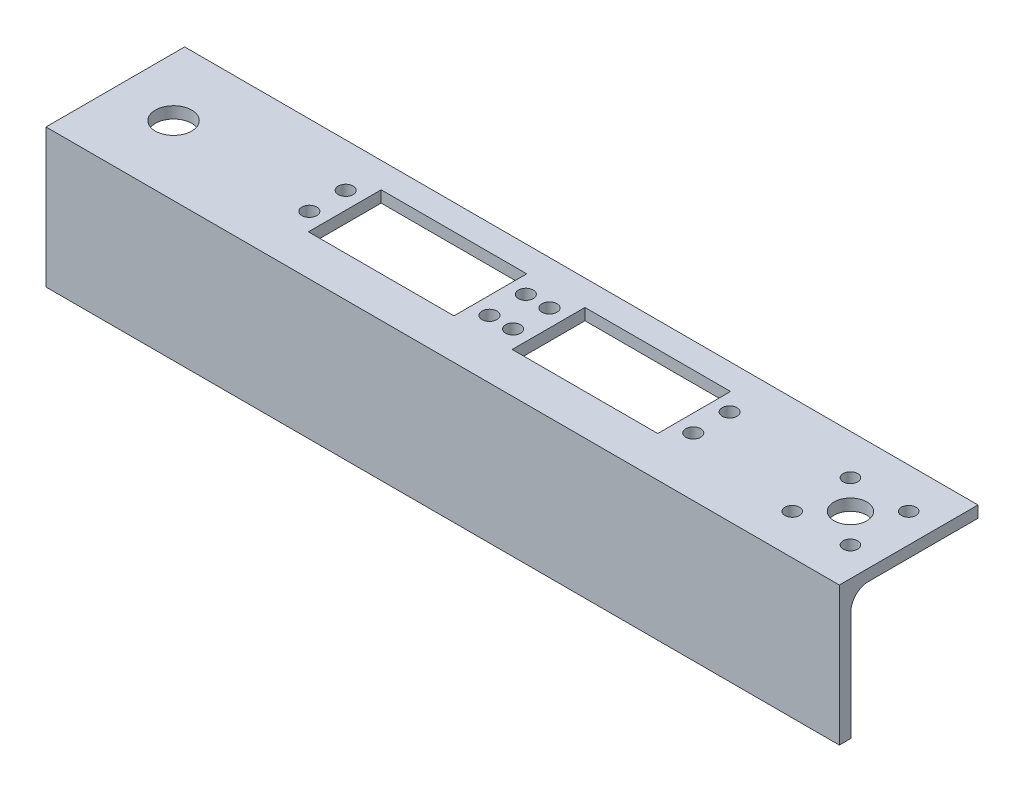
SolidWorks part; units mm, degrees
material "6061 Alloy"
ref_plane "Front Plane" through (0, 0, 0) normal (0, 0, 1) x (1, 0, 0)
ref_plane "Top Plane" through (0, 0, 0) normal (0, 1, 0) x (1, 0, 0)
ref_plane "Right Plane" through (0, 0, 0) normal (1, 0, 0) x (0, 0, -1)
sketch "Sketch1" plane through (0, 0, 0) normal (1, 0, 0) x (0, 0, -1)
  line L0 (0, 0) -> (38.1, 0)
  line L1 (38.1, 0) -> (38.1, -3.175)
  line L2 (38.1, -3.175) -> (3.175, -3.175)
  line L3 (3.175, -3.175) -> (3.175, -38.1)
  line L4 (3.175, -38.1) -> (0, -38.1)
  line L5 (0, -38.1) -> (0, 0)
  dimension "D1" = 38.1
  dimension "D3" = 3.175
extrude "Base Angle Profile" add sketch "Sketch1" along normal mid plane 218
sketch "Sketch2" plane through (0, 0, 0) normal (0, 1, 0) x (1, 0, 0)
  line L1 (-48, 31.1) -> (-8, 31.1)
  line L2 (-48, 31.1) -> (-48, 11.1)
  line L3 (-48, 11.1) -> (-8, 11.1)
  line L4 (-8, 31.1) -> (-8, 11.1)
  line L5 (-48, 31.1) -> (-8, 11.1) construction
  line L6 (-48, 11.1) -> (-8, 31.1) construction
  line L7 (8, 31.1) -> (48, 31.1)
  line L8 (8, 31.1) -> (8, 11.1)
  line L9 (8, 11.1) -> (48, 11.1)
  line L10 (48, 31.1) -> (48, 11.1)
  line L11 (8, 31.1) -> (48, 11.1) construction
  line L12 (8, 11.1) -> (48, 31.1) construction
  line L13 (-52.75, 26.1) -> (-52.75, 16.1) construction
  line L14 (-3.25, 16.1) -> (-3.25, 26.1) construction
  line L15 (3.25, 16.1) -> (3.25, 26.1) construction
  line L16 (52.75, 16.1) -> (52.75, 26.1) construction
  line L17 (109, 38.1) -> (-109, 38.1) construction
  line L18 (-3.25, 21.1) -> (3.25, 21.1) construction
  circle A0 centre (-52.75, 26.1) radius 2.05
  circle A1 centre (-52.75, 16.1) radius 2.05
  circle A2 centre (-3.25, 26.1) radius 2.05
  circle A3 centre (-3.25, 16.1) radius 2.05
  circle A4 centre (3.25, 16.1) radius 2.05
  circle A5 centre (3.25, 26.1) radius 2.05
  circle A6 centre (52.75, 26.1) radius 2.05
  circle A7 centre (52.75, 16.1) radius 2.05
  point P4 (-28, 21.1)
  point P9 (28, 21.1)
  point P10 (0, 21.1)
  point P28 (-52.75, 21.1)
  dimension "D5" = 4.1
  dimension "D1" = 20
  dimension "D2" = 40
  dimension "D3" = 16
  dimension "D6" = 4.75
  dimension "D7" = 10
  dimension "D8" = 4.75
  dimension "D9" = 4.75
  dimension "D10" = 4.75
  dimension "D11" = 7
extrude "Servo Mount Pattern" cut sketch "Sketch2" against normal through all
fillet "Internal Fillet" radius 4.7752 1 edges at (0, -3.175, -3.175)
sketch "Sketch3" plane through (0, 0, 0) normal (0, 1, 0) x (1, 0, 0)
  line L0 (93, 19.05) -> (109, 19.05) construction
  line L1 (101, 27.05) -> (85, 27.05) construction
  line L2 (101, 27.05) -> (101, 11.05) construction
  line L3 (101, 11.05) -> (85, 11.05) construction
  line L4 (85, 27.05) -> (85, 11.05) construction
  line L5 (101, 27.05) -> (85, 11.05) construction
  line L6 (101, 11.05) -> (85, 27.05) construction
  line L7 (109, 38.1) -> (109, 0) construction
  line L10 (48, 11.1) -> (48, 31.1) construction
  circle A0 centre (93, 19.05) radius 4.5
  circle A1 centre (101, 27.05) radius 2
  circle A2 centre (85, 27.05) radius 2
  circle A3 centre (85, 11.05) radius 2
  circle A4 centre (101, 11.05) radius 2
  circle A5 centre (93, 19.05) radius 16 construction
  point P7 (93, 19.05)
  dimension "D1" = 4
  dimension "D2" = 9
  dimension "D6" = 32
  dimension "D3" = 16
  dimension "D4" = 16
  dimension "D5" = 45
extrude "Lead Screw Nut Pattern" cut sketch "Sketch3" against normal blind 304.8
sketch "Sketch4" plane through (0, 0, 0) normal (0, 1, 0) x (1, 0, 0)
  line L1 (93, 19.05) -> (-93, 19.05) construction
  circle A0 centre (-93, 19.05) radius 5
  circle A1 centre (-52.75, 16.1) radius 2.05 construction
  dimension "D1" = 10
  dimension "D2" = 40.25
extrude "Cut-Extrude3" cut sketch "Sketch4" against normal through all
equation "\"Angle-Width\"= 25.4 * 1.5"
equation "\"D1@Sketch1\"=\"Angle-Width\""
equation "\"Angle-Thickness\"= 25.4 / 8"
equation "\"D3@Sketch1\"=\"Angle-Thickness\""
equation "\"D8@Sketch2\"=\"D6@Sketch2\""
equation "\"D9@Sketch2\"=\"D6@Sketch2\""
equation "\"D10@Sketch2\"=\"D6@Sketch2\""
